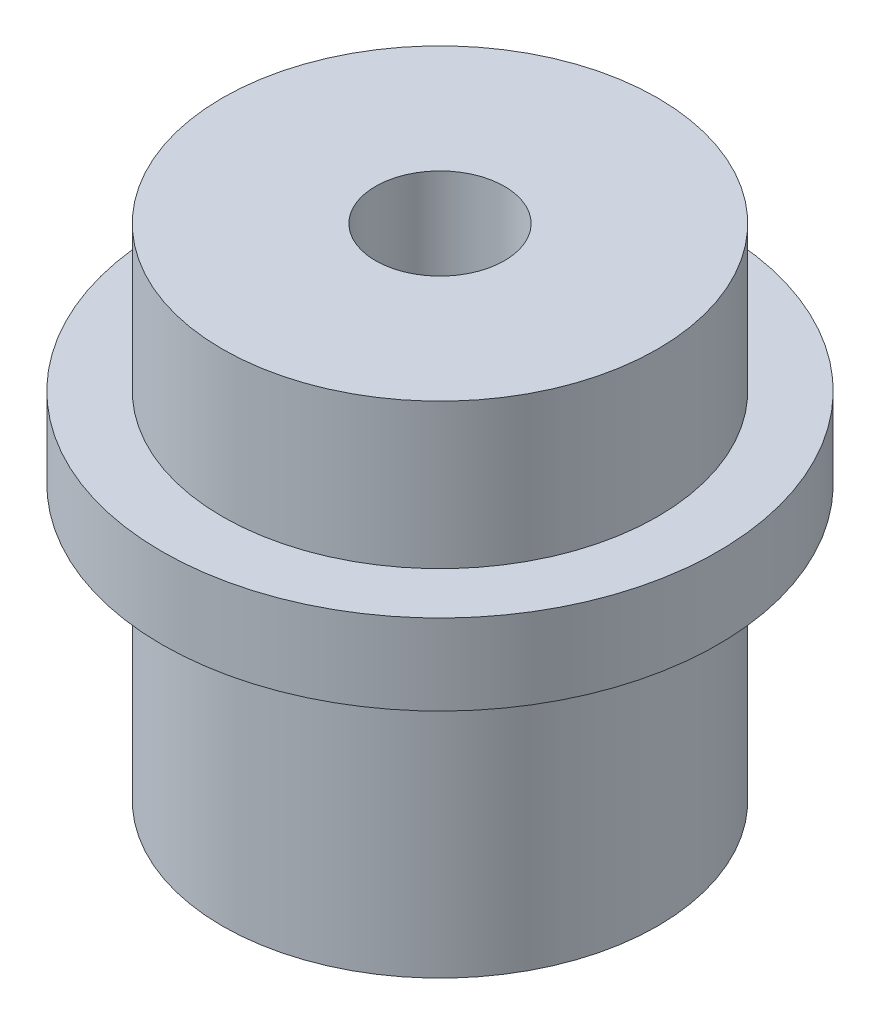
SolidWorks part; units mm, degrees
material "6061 Alloy"
ref_plane "Front Plane" through (0, 0, 0) normal (0, 0, 1) x (1, 0, 0)
ref_plane "Top Plane" through (0, 0, 0) normal (0, 1, 0) x (1, 0, 0)
ref_plane "Right Plane" through (0, 0, 0) normal (1, 0, 0) x (0, 0, -1)
sketch "Sketch1" plane through (0, 0, 0) normal (0, 1, 0) x (1, 0, 0)
  circle A0 centre (0, 0) radius 17.145
  circle A1 centre (0, 0) radius 21.9075
  dimension "D1" = 34.29
  dimension "D2" = 43.815
extrude "Boss-Extrude1" add sketch "Sketch1" along normal blind 11.43 and the other way blind 11.43 contours A0 region at (0, 0, 0)
extrude "Boss-Extrude2" add sketch "Sketch1<3>" against normal blind 6.35 separate body contours A1 A0 region at (-21.2879, 0, 0)
sketch "Sketch1<3>" plane through (0, 0, 0) normal (0, 1, 0) x (1, 0, 0) same geometry as "Sketch1"
extrude "Boss-Extrude3" add sketch "Sketch1<4>" against normal blind 27.94 contours A0 region at (0, 0, 0)
sketch "Sketch1<4>" plane through (0, 0, 0) normal (0, 1, 0) x (1, 0, 0) same geometry as "Sketch1"
sketch "Sketch2" plane through (0, -27.94, 0) normal (0, -1, 0) x (1, 0, 0)
  circle A0 centre (0, 0) radius 10.16
  circle A1 centre (0, 0) radius 21.9075
  circle A2 centre (0, 0) radius 21.9075
  circle A3 centre (0, 0) radius 17.145
  circle A4 centre (0, 0) radius 17.145
  dimension "D1" = 0
  dimension "D2" = 0
extrude "Cut-Extrude2" cut sketch "Sketch2" against normal through all both and the other way through all contours A0 region at (0, -27.94, 0)
sketch "Sketch3" plane through (0, 11.43, 0) normal (0, 1, 0) x (1, 0, 0)
  circle A0 centre (0, 0) radius 5.08
  circle A1 centre (0, 0) radius 10.16 construction
  circle A2 centre (0, 0) radius 10.16
  dimension "D1" = 10.16
extrude "Boss-Extrude4" add sketch "Sketch3" against normal up to surface (39.37 mm away) up to face at (0, -27.94, 10.16)
